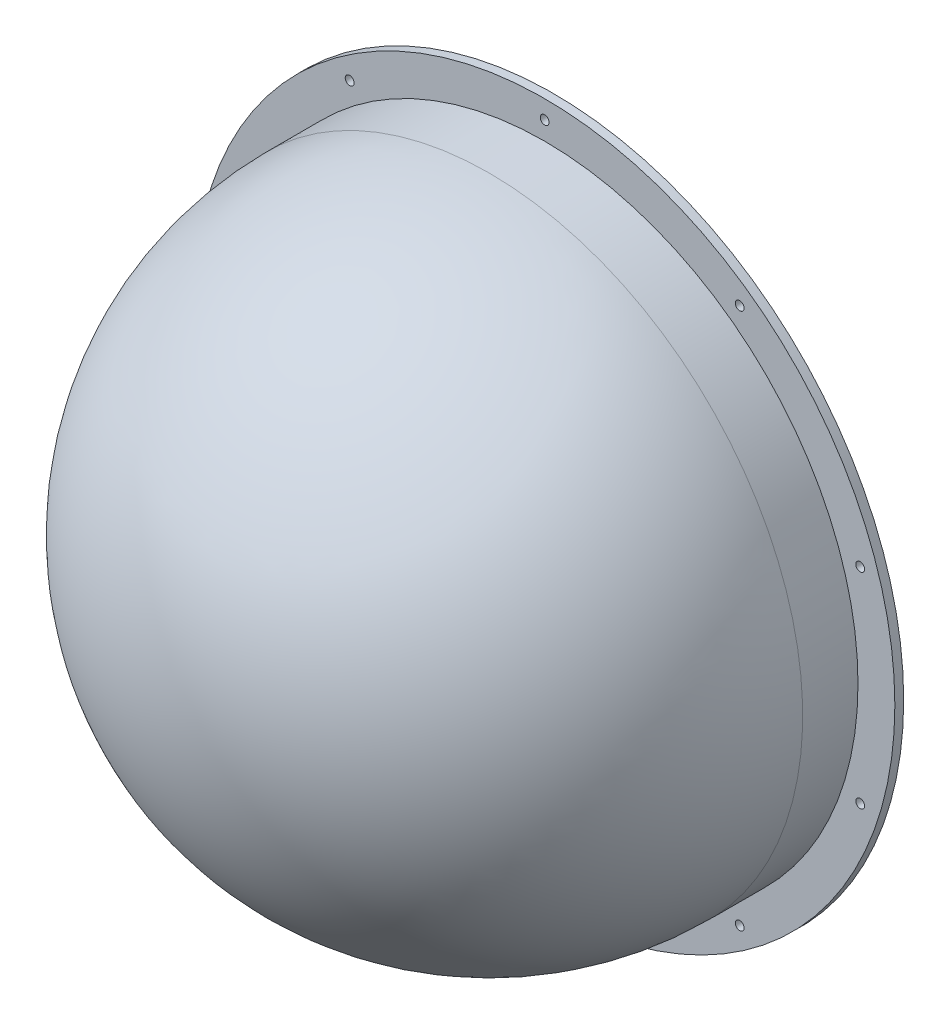
SolidWorks part; units mm, degrees
ref_plane "Front Plane" through (0, 0, 0) normal (0, 0, 1) x (1, 0, 0)
ref_plane "Top Plane" through (0, 0, 0) normal (0, 1, 0) x (1, 0, 0)
ref_plane "Right Plane" through (0, 0, 0) normal (1, 0, 0) x (0, 0, -1)
sketch "Sketch1" plane through (0, 0, 0) normal (0, 0, 1) x (1, 0, 0)
  circle A0 centre (0, 0) radius 475
  circle A1 centre (0, 0) radius 425 construction
  circle A2 centre (0, 0) radius 450 construction
  circle A3 centre (0, 450) radius 6
  circle A4 centre (264.5034, 364.0576) radius 6
  circle A5 centre (427.9754, 139.0576) radius 6
  circle A6 centre (427.9754, -139.0576) radius 6
  circle A7 centre (264.5034, -364.0576) radius 6
  circle A8 centre (0, -450) radius 6
  circle A9 centre (-264.5034, -364.0576) radius 6
  circle A10 centre (-427.9754, -139.0576) radius 6
  circle A11 centre (-427.9754, 139.0576) radius 6
  circle A12 centre (-264.5034, 364.0576) radius 6
  circle A13 centre (0, 0) radius 419
  point P28 (0, 0)
  dimension "D1" = 950
  dimension "D2" = 850
  dimension "D3" = 900
  dimension "D4" = 12
  dimension "D5" = 6
extrude "Boss-Extrude1" add sketch "Sketch1" along normal blind 12
sketch "Sketch3" plane through (0, 0, 12) normal (0, 0, 1) x (1, 0, 0)
  circle A0 centre (0, 0) radius 419
  circle A1 centre (0, 0) radius 419 construction
  circle A2 centre (0, 0) radius 425
  dimension "D1" = 6
extrude "Boss-Extrude2" [suppressed] add sketch "Sketch3" along normal blind 200 from surface
sketch "Sketch2" [suppressed] plane through (0, 0, 200) normal (0, 0, 1) x (1, 0, 0)
  line L0 (0, 300) -> (0, 294)
  line L1 (0, -294) -> (0, -300)
  arc A0 (0, 300) -> (0, -300) centre (0, 0) ccw
  circle A1 centre (0, 0) radius 300 construction
  arc A2 (0, 294) -> (0, -294) centre (0, 0) ccw
  circle A3 centre (0, 0) radius 294 construction
revolve "Revolve1" [suppressed] add sketch "Sketch2" angle 180 about L0 reverse direction yes
sketch "Sketch4" plane through (0, 0, 0) normal (1, 0, 0) x (0, 0, -1)
  line L0 (-12, 425) -> (-12, -425) construction
  line L1 (-12, 475) -> (-12, -475) construction
  line L2 (-12, 419) -> (-12, -419) construction
  line L3 (-12, 425) -> (-87, 425)
  line L4 (-12, 0) -> (-512, 0) construction
  line L5 (-12, 419) -> (-87, 419)
  line L6 (-512, 0) -> (-506, 0)
  line L7 (-12, 425) -> (-12, 419)
  arc A0 (-87, 425) -> (-512, 0) centre (-87, 0) ccw
  arc A1 (-87, 419) -> (-506, 0) centre (-87, 0) ccw
  point P6 (-12, 0)
  dimension "D3" = 425
  dimension "D1" = 850
  dimension "D2" = 6
  dimension "D4" = 6
  dimension "D5" = 500
revolve "Revolve2" add sketch "Sketch4" angle 360 about L4
equation "\"mbtOD\" = 850"
equation "\"mbtT\" = 6"
equation "\"mbtL\" = 1500"
equation "\"mbtFlangeOD\" = 950"
equation "\"mbtFlangeT\" = 12"
equation "\"mbtFlangeHoleDia\" = 12"
equation "\"D1@Sketch1\"=\"mbtFlangeOD\""
equation "\"D2@Sketch1\"=\"mbtOD\""
equation "\"D3@Sketch1\"=(\"mbtFlangeOD\"+\"mbtOD\")/2"
equation "\"D4@Sketch1\"=\"mbtFlangeHoleDia\""
equation "\"D1@Boss-Extrude1\"=\"mbtFlangeT\""
equation "\"D5@Sketch1\"=\"mbtT\""
equation "\"D1@Sketch3\"=\"mbtT\""
equation "\"mbtFlangeBoltCircleDia\" = 650"
equation "\"mbtOringSize\" = 10 "
equation "\"mbtOringDia\" = 620"
equation "\"mbtWidth\" = 2250"
equation "\"skiWidth\" = 1250"
equation "\"D1@Sketch4\"=\"mbtOD\""
equation "\"D2@Sketch4\"=\"mbtT\""
equation "\"D3@Sketch4\"=\"mbtOD\"/2"
equation "\"D4@Sketch4\"=\"mbtT\""
equation "\"mbtCapL\" = 500"
equation "\"D5@Sketch4\"=\"mbtCapL\""
